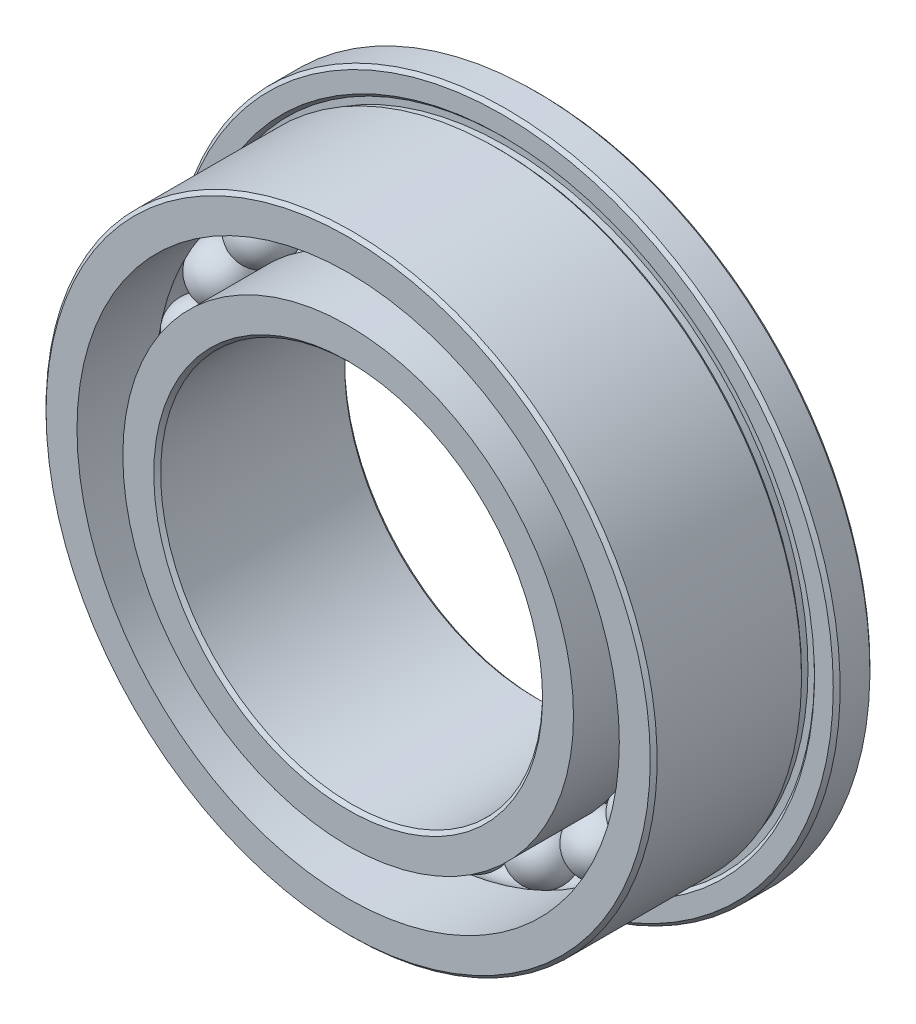
SolidWorks part; units mm, degrees
ref_plane "Front Plane" through (0, 0, 0) normal (0, 0, 1) x (1, 0, 0)
ref_plane "Top Plane" through (0, 0, 0) normal (0, 1, 0) x (1, 0, 0)
ref_plane "Right Plane" through (0, 0, 0) normal (1, 0, 0) x (0, 0, -1)
sketch "Sketch1" plane through (0, 0, 0) normal (1, 0, 0) x (0, 0, -1)
  line L0 (0, 6.35) -> (0, -6.35) construction
  line L1 (-1.9844, 6.35) -> (1.9844, 6.35) construction
  line L2 (0, 0) -> (1.9844, 0) construction
  line L3 (1.9844, 6.9469) -> (1.9844, -6.9469) construction
  line L4 (1.9844, -6.9469) -> (1.2224, -6.9469) construction
  line L5 (1.9844, 3.9688) -> (0, 3.9688) construction
  line L6 (1.9844, 3.9688) -> (1.9844, -3.9688) construction
  dimension "OD" = 12.7
  dimension "Width" = 3.9688
  dimension "Flange Dia." = 13.8938
  dimension "Flange Thickness" = 0.762
  dimension "ID" = 7.9375
sketch "Sketch2" plane through (0, 0, 0) normal (1, 0, 0) x (0, 0, -1)
  line L0 (1.9844, 6.9469) -> (1.2224, 6.9469)
  line L1 (1.2224, 6.9469) -> (1.2224, 6.4847)
  line L2 (1.0877, 6.35) -> (-1.9844, 6.35)
  line L3 (-1.9844, 6.35) -> (-1.9844, 5.6356)
  line L4 (-1.9844, 5.6356) -> (-0.3572, 5.6356)
  line L5 (1.9844, 6.9469) -> (1.9844, -6.9469) construction
  line L6 (1.9844, 5.6356) -> (1.9844, 6.9469)
  line L7 (1.9844, 3.9688) -> (-1.9844, 3.9688)
  line L8 (-1.9844, 3.9688) -> (-1.9844, 4.6831)
  line L9 (-1.9844, 4.6831) -> (-0.3572, 4.6831)
  line L10 (1.9844, 4.6831) -> (1.9844, 3.9688)
  line L11 (0, 6.35) -> (0, 3.9688) construction
  line L12 (-0.5953, 5.1594) -> (0.5953, 5.1594) construction
  line L13 (0.3572, 5.6356) -> (1.9844, 5.6356)
  line L14 (0.3572, 4.6831) -> (1.9844, 4.6831)
  line L15 (1.2224, 6.4847) -> (1.2897, 6.4174)
  line L16 (1.2897, 6.4174) -> (1.2897, 6.2826)
  line L17 (1.2897, 6.2826) -> (1.155, 6.2826)
  line L18 (1.155, 6.2826) -> (1.0877, 6.35)
  line L19 (1.2224, 6.35) -> (1.2897, 6.2826) construction
  line L20 (1.2897, 6.4174) -> (1.155, 6.2826) construction
  line L21 (1.0877, 6.35) -> (1.2224, 6.35) construction
  line L22 (1.2224, 6.35) -> (1.2224, 6.4847) construction
  circle A0 centre (0, 5.1594) radius 0.5953 construction
  arc A1 (-0.3572, 5.6356) -> (0.3572, 5.6356) centre (0, 5.1594) cw
  arc A2 (-0.3572, 4.6831) -> (0.3572, 4.6831) centre (0, 5.1594) ccw
  dimension "D1" = 2.3812
  dimension "Ball Dia." = 1.1906
  dimension "D2" = 135
  dimension "D3" = 0.1905
  dimension "D4" = 0.9525
  dimension "Race Thickness" = 0.7144
revolve "Revolve1" add sketch "Sketch2" angle 360 about L2
fillet "Fillet1" radius 0.0714 3 edges at (0, -6.9469, -1.9844) (0, -6.9469, -1.2224) (0, -6.35, 1.9844) profile chamfer
sketch "Sketch3" plane through (0, 0, 0) normal (0, 0, 1) x (1, 0, 0)
  line L0 (-3.9688, 0) -> (3.9688, 0) construction
  line L1 (-6.35, 0) -> (6.35, 0) construction
  point P5 (0, 0)
  dimension "ID2" = 7.9375
  dimension "OD2" = 12.7
fillet "Fillet2" radius 0.0714 2 edges at (0, -3.9688, -1.9844) (0, -3.9688, 1.9844) profile chamfer
sketch "Sketch7" plane through (0, 0, 0) normal (0, 0, 1) x (1, 0, 0)
  line L0 (0, 5.7547) -> (0, 4.5641)
  line L1 (0, 6.9469) -> (0, -6.9469) construction
  line L2 (-0.6685, 5.7547) -> (0, 0) construction
  line L3 (0, 0) -> (0.6685, 5.7547) construction
  line L4 (0.6685, 5.7547) -> (-0.6685, 5.7547) construction
  circle A0 centre (0, 5.1594) radius 0.5953 construction
  circle A1 centre (0, 0) radius 5.7547 construction
  circle A2 centre (0, 0) radius 4.5641 construction
  arc A4 (0, 5.7547) -> (0, 4.5641) centre (0, 5.1594) ccw
  dimension "D1" = 13.252
revolve "Revolve3" add sketch "Sketch7" angle 360 about L0
pattern_circular "CirPattern3" count 23 over 360 about axis through (0, 0, 0) along (0, 0, -1) of bodies 107
sketch "Sketch8" [suppressed] plane through (0, 0, 0) normal (1, 0, 0) x (0, 0, -1)
  line L1 (-1.1906, 2.0241) -> (-1.0477, 2.0241)
  line L2 (-1.1906, 2.0241) -> (-1.1906, 2.1431)
  line L3 (-1.1906, 2.1431) -> (-1.0477, 2.1431)
  line L4 (-1.0477, 2.0241) -> (-1.0477, 2.1431)
  line L5 (1.1906, 2.0241) -> (1.0478, 2.0241)
  line L6 (1.1906, 2.0241) -> (1.1906, 2.1431)
  line L7 (1.1906, 2.1431) -> (1.0478, 2.1431)
  line L8 (1.0478, 2.0241) -> (1.0478, 2.1431)
  line L9 (1.1906, 1.5478) -> (1.0478, 1.5478)
  line L10 (1.1906, 1.5478) -> (1.1906, 1.4287)
  line L11 (1.1906, 1.4287) -> (1.0478, 1.4287)
  line L12 (1.0478, 1.5478) -> (1.0478, 1.4287)
  line L13 (-1.1906, 1.5478) -> (-1.0477, 1.5478)
  line L14 (-1.1906, 1.5478) -> (-1.1906, 1.4287)
  line L15 (-1.1906, 1.4287) -> (-1.0477, 1.4287)
  line L16 (-1.0477, 1.5478) -> (-1.0477, 1.4287)
  dimension "D1" = 0.2381
  dimension "D2" = 0.2858
revolve "Cut-Revolve1" [suppressed] cut sketch "Sketch8" angle 360 about L2
sketch "Sketch9" [suppressed] plane through (0, 0, 0) normal (1, 0, 0) x (0, 0, -1)
  line L0 (-1.0477, 2.1431) -> (-1.0477, 1.8657)
  line L1 (-1.0477, 1.8657) -> (-1.1192, 1.7419)
  line L2 (-1.1192, 1.7419) -> (-1.1192, 1.4645)
  line L3 (1.1192, 1.4645) -> (1.1192, 1.4287) construction
  line L4 (1.0478, 2.1431) -> (1.0478, 1.8657)
  line L5 (1.0478, 1.8657) -> (1.1192, 1.7419)
  line L6 (1.1192, 1.7419) -> (1.1192, 1.4645)
  line L7 (1.1906, 1.4287) -> (1.0478, 1.4287) construction
  line L8 (-1.0835, 2.1431) -> (-1.0835, 1.8752)
  line L9 (-1.0835, 1.8752) -> (-1.1549, 1.7515)
  line L10 (-1.1549, 1.7515) -> (-1.1549, 1.4645)
  line L11 (-1.0477, 2.1431) -> (-1.0835, 2.1431)
  line L12 (-1.1192, 1.4645) -> (-1.1549, 1.4645)
  line L13 (1.0835, 2.1431) -> (1.0835, 1.8752)
  line L14 (1.0835, 1.8752) -> (1.1549, 1.7515)
  line L15 (1.1549, 1.7515) -> (1.1549, 1.4645)
  line L16 (1.0478, 2.1431) -> (1.0835, 2.1431)
  line L17 (1.1192, 1.4645) -> (1.1549, 1.4645)
  line L18 (-1.0477, 1.8657) -> (-1.0477, 2.6) construction
  line L19 (1.0478, 1.8657) -> (1.0478, 2.1431) construction
  line L20 (-1.0477, 1.4287) -> (-1.1906, 1.4287) construction
  line L22 (-1.1192, 1.4645) -> (-1.1192, 1.4287) construction
  dimension "D2" = 150
  dimension "D1" = 150
  dimension "D5" = 0.1429
  dimension "D3" = 0.0357
  dimension "D4" = 0.0357
revolve "Revolve4" [suppressed] add sketch "Sketch9" angle 360 about L2
ref_axis "Center Axis 1" through (0, 0, -0.8731) along (0, 0, 1)
ref_plane "Contact Plane 1" through (0, 0, -1.2224) normal (0, 0, 1) x (1, 0, 0)
equation "\"Ball Dia.@Sketch2\"=\"D1@Sketch2\"*.5"
equation "\"D3@Sketch2\"=\"Flange Thickness@Sketch1\"/4"
equation "\"D1@Fillet1\"=\"Race Thickness@Sketch2\"/10"
equation "\"ID2@Sketch3\" = \"ID@Sketch1\""
equation "\"OD2@Sketch3\" = \"OD@Sketch1\""
equation "\"D1@Fillet2\"=\"Race Thickness@Sketch2\"/10"
equation "\"D1@CirPattern3\"=360/\"D1@Sketch7\"-4"
equation "\"D1@Sketch8\"=\"Race Thickness@Sketch2\"/3"
equation "\"D2@Sketch8\"=\"Race Thickness@Sketch2\"/2.5"
equation "\"D3@Sketch9\"=\"D5@Sketch9\"/4"
equation "\"D4@Sketch9\"=\"D5@Sketch9\"/4"
equation "\"D1@Sketch9\"=\"D2@Sketch9\""
equation "\"D4@Sketch2\"=\"D1@Sketch2\"*.4"
